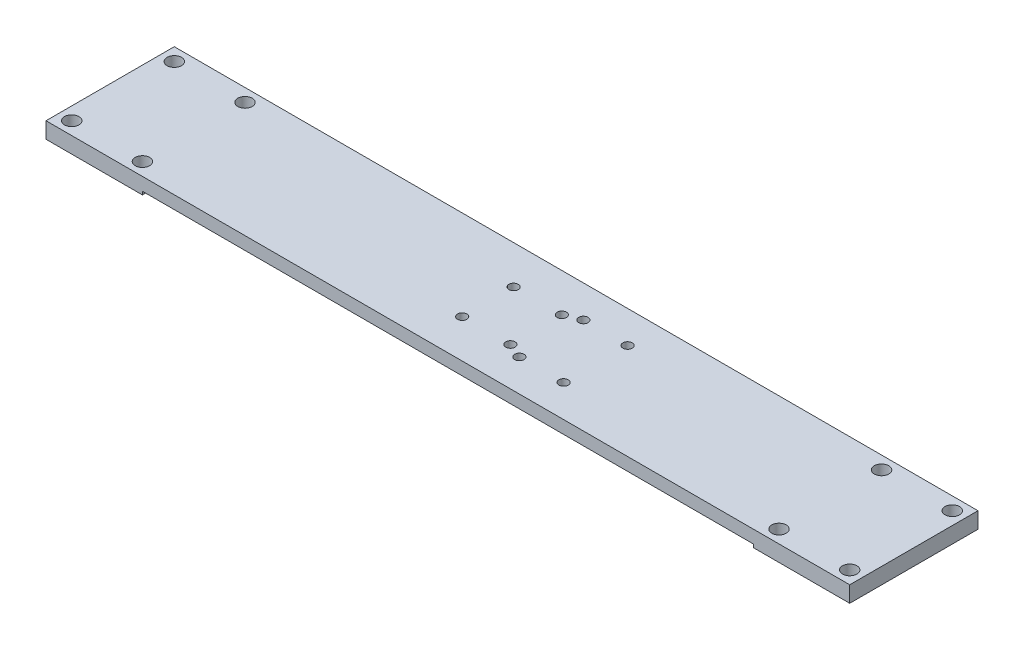
SolidWorks part; units mm, degrees
ref_plane "前视基准面" through (0, 0, 0) normal (0, 0, 1) x (1, 0, 0)
ref_plane "上视基准面" through (0, 0, 0) normal (0, 1, 0) x (1, 0, 0)
ref_plane "右视基准面" through (0, 0, 0) normal (1, 0, 0) x (0, 0, -1)
other "Configuration Table"
sketch "草图1" plane through (0, 0, 0) normal (0, 1, 0) x (1, 0, 0)
  line L1 (0, 0) -> (-250, 0)
  line L2 (0, 0) -> (0, 39.9)
  line L3 (0, 39.9) -> (-250, 39.9)
  line L4 (-250, 0) -> (-250, 39.9)
  dimension "D1" = 39.9
  dimension "D2" = 250
extrude "凸台-拉伸1" add sketch "草图1" along normal blind 4
sketch "草图2" plane through (0, 4, 0) normal (0, 1, 0) x (1, 0, 0)
  line L0 (0, 39.9) -> (-250, 39.9) construction
  line L1 (-135, 39.9) -> (-115, 39.9) construction
  line L2 (-135, 39.9) -> (-135, 0) construction
  line L3 (-135, 0) -> (-115, 0) construction
  line L4 (-115, 39.9) -> (-115, 0) construction
  line L5 (-250, 0) -> (0, 0) construction
  line L6 (-250, 39.9) -> (-250, 0) construction
  line L7 (-135, 39.9) -> (-132.5, 39.9) construction
  line L8 (-132.5, 39.9) -> (-132.5, 27.95) construction
  line L9 (-132.5, 27.95) -> (-132.5, 11.95) construction
  line L10 (-132.5, 11.95) -> (-117.5, 11.95) construction
  line L11 (-117.5, 11.95) -> (-117.5, 27.95) construction
  circle A0 centre (-132.5, 27.95) radius 1.45
  circle A1 centre (-117.5, 27.95) radius 1.45
  circle A2 centre (-117.5, 11.95) radius 1.45
  circle A3 centre (-132.5, 11.95) radius 1.45
  dimension "D8" = 2.9
  dimension "D9" = 2.9
  dimension "D10" = 2.9
  dimension "D11" = 2.9
  dimension "D1" = 20
  dimension "D2" = 115
  dimension "D3" = 2.5
  dimension "D4" = 11.95
  dimension "D5" = 16
  dimension "D6" = 15
  dimension "D7" = 16
extrude "切除-拉伸1" cut sketch "草图2" against normal blind 12
extrude "切除-拉伸2" cut sketch "草图3" against normal blind 12
sketch "草图3" plane through (-275.0918, 0, 105.3762) normal (0, -1, 0) x (-1, 0, 0.0018)
  circle A4 centre (-162.5539, 115.0772) radius 1.45
  circle A5 centre (-162.5905, 134.9771) radius 1.45
  circle A6 centre (-176.3039, 115.0519) radius 1.45
  circle A7 centre (-176.3405, 134.9518) radius 1.45
sketch "草图7" plane through (0, 4, 0) normal (0, 1, 0) x (1, 0, 0)
  line L0 (-250, 39.9) -> (-246, 39.9) construction
  line L1 (0, 39.9) -> (-250, 39.9) construction
  line L2 (-246, 39.9) -> (-246, 35.9) construction
  line L3 (-246, 35.9) -> (-224, 35.9) construction
  line L4 (-250, 19.95) -> (-131.5357, 19.95) construction
  line L5 (-250, 39.9) -> (-250, 0) construction
  line L6 (-125, 39.9) -> (-125, 25.1167) construction
  line L7 (0, 19.95) -> (-118.4643, 19.95) construction
  line L8 (-4, 35.9) -> (-26, 35.9) construction
  line L9 (-4, 39.9) -> (-4, 35.9) construction
  line L10 (0, 39.9) -> (-4, 39.9) construction
  circle A0 centre (-246, 35.9) radius 2.25
  circle A1 centre (-224, 35.9) radius 2.25
  circle A2 centre (-224, 4) radius 2.25
  circle A3 centre (-246, 4) radius 2.25
  circle A4 centre (-4, 4) radius 2.25
  circle A5 centre (-26, 4) radius 2.25
  circle A6 centre (-26, 35.9) radius 2.25
  circle A7 centre (-4, 35.9) radius 2.25
  dimension "D4" = 4.5
  dimension "D5" = 4.5
  dimension "D1" = 4
  dimension "D2" = 4
  dimension "D3" = 22
extrude "切除-拉伸6" cut sketch "草图7" against normal blind 20
sketch "草图8" plane through (0, 0, 0) normal (0, -1, 0) x (1, 0, 0)
  line L0 (0, -39.9) -> (-250, -39.9) construction
  line L1 (-250, 0) -> (-220, 0)
  line L2 (-250, 0) -> (-250, -39.9)
  line L3 (-250, -39.9) -> (-220, -39.9)
  line L4 (-220, 0) -> (-220, -39.9)
  line L6 (0, 0) -> (-30, 0)
  line L7 (0, 0) -> (0, -39.9)
  line L8 (0, -39.9) -> (-30, -39.9)
  line L9 (-30, 0) -> (-30, -39.9)
  circle A0 centre (-4, -35.9) radius 2.25 construction
  circle A1 centre (-26, -35.9) radius 2.25 construction
  circle A2 centre (-4, -4) radius 2.25 construction
  circle A3 centre (-26, -4) radius 2.25 construction
  circle A4 centre (-224, -35.9) radius 2.25 construction
  circle A5 centre (-246, -35.9) radius 2.25 construction
  circle A6 centre (-224, -4) radius 2.25 construction
  circle A7 centre (-246, -4) radius 2.25 construction
  circle A8 centre (-4, -35.9) radius 2.25
  circle A9 centre (-26, -35.9) radius 2.25
  circle A10 centre (-4, -4) radius 2.25
  circle A11 centre (-26, -4) radius 2.25
  circle A12 centre (-224, -35.9) radius 2.25
  circle A13 centre (-246, -35.9) radius 2.25
  circle A14 centre (-224, -4) radius 2.25
  circle A15 centre (-246, -4) radius 2.25
  dimension "D1" = 30
  dimension "D2" = 30
extrude "凸台-拉伸2" add sketch "草图8" along normal blind 1
